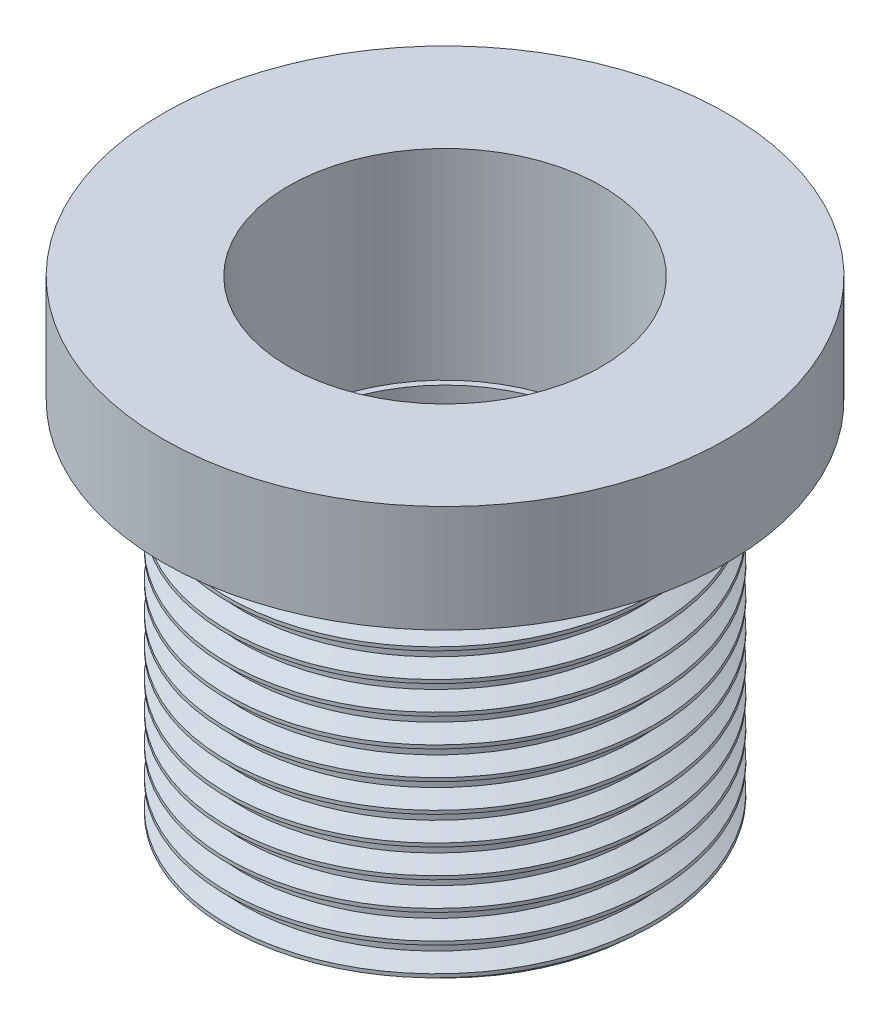
SolidWorks part; units mm, degrees
ref_plane "Front Plane" through (0, 0, 0) normal (0, 0, 1) x (1, 0, 0)
ref_plane "Top Plane" through (0, 0, 0) normal (0, 1, 0) x (1, 0, 0)
ref_plane "Right Plane" through (0, 0, 0) normal (1, 0, 0) x (0, 0, -1)
sketch "Sketch1" plane through (0, 0, 0) normal (0, 1, 0) x (1, 0, 0)
  circle A0 centre (0, 0) radius 15.9
  dimension "D1" = 31.8
extrude "Boss-Extrude1" add sketch "Sketch1" along normal blind 35
sketch "Sketch2" plane through (0, 0, 0) normal (0, -1, 0) x (1, 0, 0)
  circle A0 centre (0, 0) radius 11.7
  dimension "D1" = 23.4
extrude "Cut-Extrude1" cut sketch "Sketch2" against normal blind 15
sketch "Sketch3" plane through (0, 35, 0) normal (0, 1, 0) x (1, 0, 0)
  circle A0 centre (0, 0) radius 11.7
  dimension "D1" = 23.4
extrude "Cut-Extrude2" cut sketch "Sketch3" against normal blind 15
sketch "Sketch4" plane through (0, 20, 0) normal (0, 1, 0) x (1, 0, 0)
  circle A0 centre (0, 0) radius 11.25
  dimension "D1" = 22.5
extrude "Cut-Extrude3" cut sketch "Sketch4" against normal blind 13
sketch "Sketch5" plane through (0, 35, 0) normal (0, 1, 0) x (1, 0, 0)
  circle A0 centre (0, 0) radius 15.9
  circle A1 centre (0, 0) radius 21.0878
extrude "Boss-Extrude2" add sketch "Sketch5" against normal blind 8
thread "Thread1" pitch 2.1167 method cut profile "Thread Profile1" start angle 0, offset 5, length 30, pitch 2.1167, diameter 31.8
ref_plane "Plane1" through (15.9, -5, 0) normal (0, 0, 1) x (1, 0, 0)
sketch "Thread Profile1" plane through (15.9, -5, 0) normal (0, 0, 1) x (1, 0, 0)
  line L0 (0, 0) -> (0, 2.1167) construction
  line L11 (0, 0) -> (0, 1.8521)
  line L12 (0, 1.8521) -> (-1.1457, 1.1906)
  line L13 (-1.1457, 1.1906) -> (-1.1457, 0.6615)
  line L15 (-1.1457, 0.6615) -> (0, 0)
  line L17 (-1.1457, 0.926) -> (0, 0.926) construction
  point P2 (0, 0)
  dimension "Pitch" = 2.1167
  dimension "Profile_Angle" = 60
  dimension "Profile_Land" = 0.5292
  dimension "Profile_Height" = 1.1457
